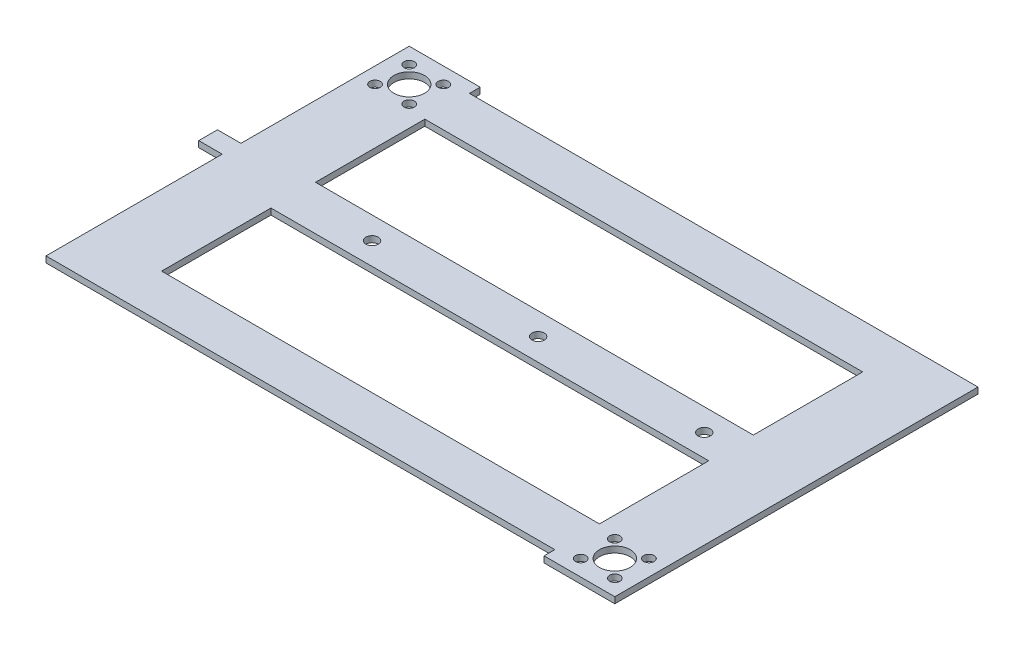
SolidWorks part; units mm, degrees
ref_plane "Front Plane" through (0, 0, 0) normal (0, 0, 1) x (1, 0, 0)
ref_plane "Top Plane" through (0, 0, 0) normal (0, 1, 0) x (1, 0, 0)
ref_plane "Right Plane" through (0, 0, 0) normal (1, 0, 0) x (0, 0, -1)
sketch "Sketch1" plane through (0, 0, 0) normal (0, 1, 0) x (1, 0, 0)
  line L0 (-95.0509, 92.8338) -> (57.8211, 92.8338) construction
  line L1 (-91.977, 142.8838) -> (-86.977, 142.8838) construction
  line L2 (-86.977, 142.8838) -> (-91.977, 142.8838) construction
  line L3 (67.7305, 150.1338) -> (82.2305, 150.1338)
  line L4 (-99.227, 35.5316) -> (-84.727, 35.5316)
  line L5 (-84.727, 35.5316) -> (62.7305, 35.5316)
  line L6 (-79.6432, 50.0316) -> (62.7305, 50.0316)
  line L7 (-79.6432, 150.1338) -> (67.7305, 150.1338)
  line L8 (-79.6432, 135.6338) -> (62.7305, 135.6338)
  line L9 (-79.6432, 100.0827) -> (62.7305, 100.0827)
  line L10 (-79.6432, 85.5827) -> (62.7305, 85.5827)
  line L17 (-84.6432, 153.6338) -> (-79.6432, 153.6338)
  line L18 (-84.6432, 153.6338) -> (-102.727, 153.6338)
  line L19 (-102.727, 100.0827) -> (-102.727, 153.6338)
  line L20 (-79.6432, 153.4321) -> (-79.6432, 150.1338)
  line L21 (-79.6432, 135.6338) -> (-79.6432, 100.0827)
  line L22 (-79.6432, 85.5827) -> (-79.6432, 50.0316)
  line L23 (-102.727, 85.5827) -> (-102.727, 35.5316)
  line L24 (-102.727, 35.5316) -> (-99.227, 35.5316)
  line L25 (67.7305, 32.0316) -> (62.7305, 32.0316)
  line L26 (67.7305, 32.0316) -> (85.7305, 32.0316)
  line L27 (85.7305, 50.0316) -> (85.7305, 32.0316)
  line L28 (62.7305, 32.0316) -> (62.7305, 35.5316)
  line L29 (62.7305, 50.0316) -> (62.7305, 85.5827)
  line L30 (62.7305, 100.0827) -> (62.7305, 135.6338)
  line L31 (85.7305, 50.0316) -> (85.7305, 85.5827)
  line L32 (85.7305, 100.0827) -> (85.7305, 150.1338)
  line L33 (85.7305, 150.1338) -> (82.2305, 150.1338)
  line L34 (-79.6432, 153.4321) -> (-79.6432, 153.6338)
  line L35 (0, -55) -> (0, 55) construction
  line L36 (-102.727, 100.0827) -> (-102.727, 98.9236)
  line L37 (85.7305, 100.0827) -> (85.7305, 85.5827)
  line L38 (-102.727, 92.8327) -> (-110.3584, 92.8327)
  line L39 (-110.3584, 92.8327) -> (-110.3584, 98.9236)
  line L40 (-110.3584, 98.9236) -> (-102.727, 98.9236)
  line L41 (-102.727, 92.8327) -> (-102.727, 85.5827)
  circle A0 centre (-91.977, 142.8838) radius 5
  circle A1 centre (74.9805, 42.7816) radius 5
  circle A2 centre (-86.427, 148.4338) radius 1.7
  circle A3 centre (-97.527, 148.4338) radius 1.7
  circle A4 centre (-86.427, 137.3338) radius 1.7
  circle A5 centre (-97.527, 137.3338) radius 1.7
  circle A6 centre (69.4305, 48.3316) radius 1.7
  circle A7 centre (80.5305, 48.3316) radius 1.7
  circle A8 centre (80.5305, 37.2316) radius 1.7
  circle A9 centre (69.4305, 37.2316) radius 1.7
  circle A10 centre (-54, 92.8338) radius 2
  circle A11 centre (0, 92.8338) radius 2
  circle A13 centre (54, 92.8338) radius 2
  dimension "D1" = 3.4
  dimension "D2" = 3.4
  dimension "D5" = 4
  dimension "D6" = 4
  dimension "D7" = 4
  dimension "D8" = 54
  dimension "D3" = 5
  dimension "D4" = 5
  dimension "D9" = 54
  dimension "D10" = 0
extrude "Boss-Extrude1" add sketch "Sketch1" along normal blind 2
